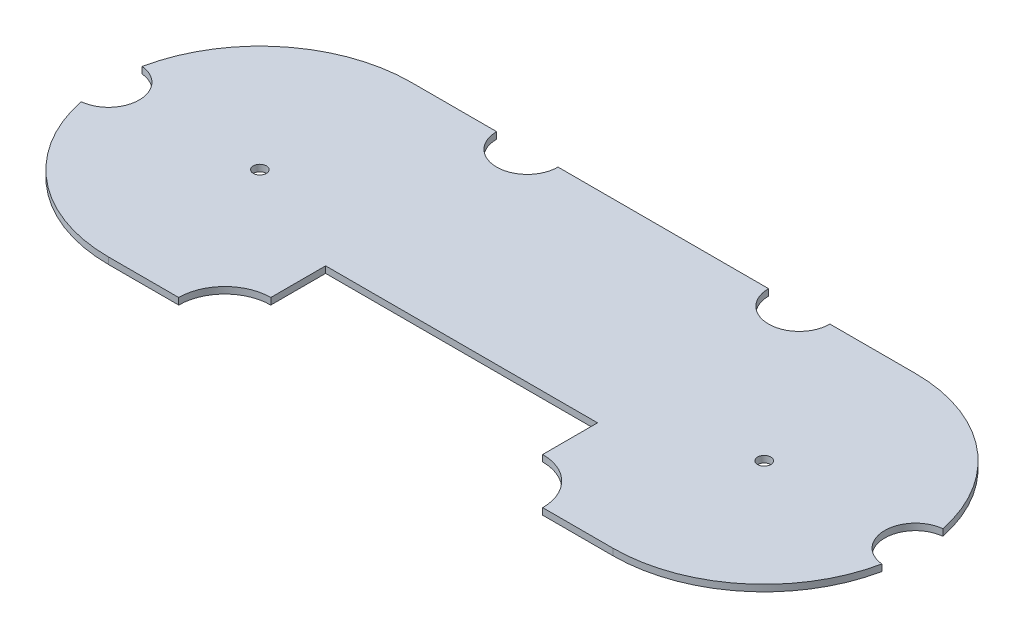
SolidWorks part; units mm, degrees
ref_plane "Front Plane" through (0, 0, 0) normal (0, 0, 1) x (1, 0, 0)
ref_plane "Top Plane" through (0, 0, 0) normal (0, 1, 0) x (1, 0, 0)
ref_plane "Right Plane" through (0, 0, 0) normal (1, 0, 0) x (0, 0, -1)
sketch "Sketch1" plane through (0, 0, 0) normal (0, 1, 0) x (1, 0, 0)
  line L0 (0, 0) -> (0, 34.5) construction
  line L1 (0, 34.5) -> (-24, 34.5)
  line L2 (0, 34.5) -> (24, 34.5)
  line L3 (-57.5, 34.5) -> (-57.5, -34.5) construction
  line L4 (57.5, 34.5) -> (57.5, -34.5) construction
  line L5 (-57.5, -34.5) -> (-41.5, -34.5)
  line L6 (0, 0) -> (0, -11.5) construction
  line L7 (-57.5, 0) -> (-85, 0) construction
  line L8 (57.5, 0) -> (85, 0) construction
  line L9 (-57.5, 0) -> (0, 0) construction
  line L10 (0, 0) -> (57.5, 0) construction
  line L11 (-31, -24) -> (-31, -11.5)
  line L12 (-31, -11.5) -> (31, -11.5)
  line L13 (31, -11.5) -> (31, -24)
  line L14 (41.5, -34.5) -> (57.5, -34.5)
  line L15 (-41.5, -34.5) -> (-41.5, -35.5) construction
  line L16 (-31, -24) -> (31, -24) construction
  line L17 (41.5, -34.5) -> (41.5, -35.5) construction
  line L18 (-31, -11.5) -> (-31, 27.5) construction
  line L19 (31, -11.5) -> (31, 27.5) construction
  line L20 (-38, 34.5) -> (-57.5, 34.5)
  line L21 (38, 34.5) -> (57.5, 34.5)
  line L22 (24, 34.5) -> (24, 37.8436) construction
  line L23 (38, 34.5) -> (38, 37.8436) construction
  line L24 (31, 27.5) -> (31, 34.5) construction
  line L25 (-31, 27.5) -> (-31, 34.5) construction
  line L26 (-38, 34.5) -> (-38, 36.7711) construction
  line L27 (-24, 34.5) -> (-24, 36.7711) construction
  line L28 (-91.2899, 6.9639) -> (-91.2899, -6.9639) construction
  line L29 (85, 0) -> (92, 0) construction
  line L30 (-85, 0) -> (-92, 0) construction
  arc A0 (-57.5, 34.5) -> (-91.2899, 6.9639) centre (-57.5, 0) ccw
  arc A1 (57.5, 34.5) -> (91.2899, 6.9639) centre (57.5, 0) cw
  arc A2 (-41.5, -34.5) -> (-31, -24) centre (-31, -34.5) cw
  arc A3 (31, -24) -> (41.5, -34.5) centre (31, -34.5) cw
  arc A4 (-91.2899, 6.9639) -> (-91.2899, -6.9639) centre (-92, 0) cw
  arc A5 (24, 34.5) -> (38, 34.5) centre (31, 34.5) ccw
  arc A6 (-38, 34.5) -> (-24, 34.5) centre (-31, 34.5) ccw
  arc A7 (91.2899, 6.9639) -> (91.2899, -6.9639) centre (92, 0) ccw
  arc A8 (-91.2899, -6.9639) -> (-57.5, -34.5) centre (-57.5, 0) ccw
  arc A9 (91.2899, -6.9639) -> (57.5, -34.5) centre (57.5, 0) cw
  arc A10 (-91.2899, 6.9639) -> (-91.2899, -6.9639) centre (-57.5, 0) ccw construction
  arc A11 (91.2899, 6.9639) -> (90.8072, -8.9932) centre (57.5, 0) cw construction
  circle A12 centre (-57.5, 0) radius 1.5
  circle A13 centre (57.5, 0) radius 1.5
  point P14 (0, -11.5)
  dimension "D5" = 10.5
  dimension "D8" = 7
  dimension "D9" = 3
  dimension "D1" = 69
  dimension "D2" = 184
  dimension "D3" = 23
  dimension "D4" = 62
  dimension "D6" = 1
  dimension "D7" = 1
extrude "Boss-Extrude1" add sketch "Sketch1" along normal blind 1.5
